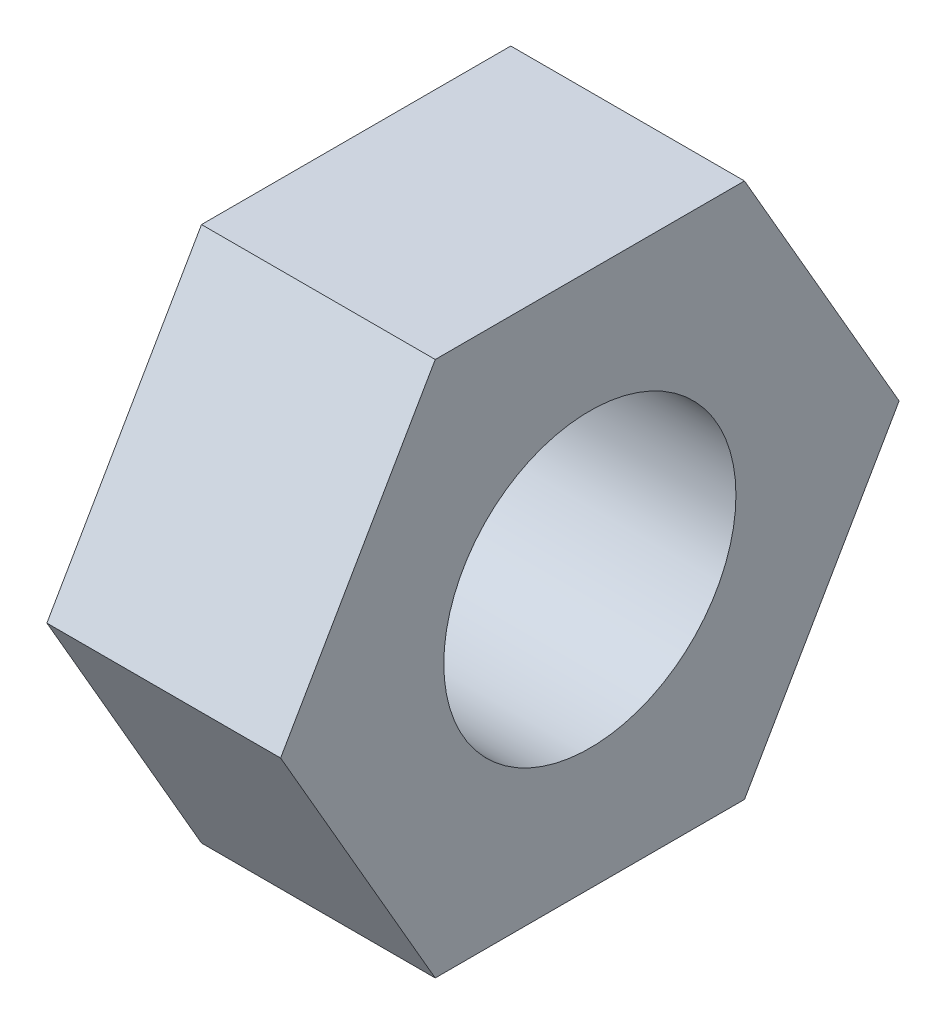
SolidWorks part; units mm, degrees
ref_plane "Front Plane" through (0, 0, 0) normal (0, 0, 1) x (1, 0, 0)
ref_plane "Top Plane" through (0, 0, 0) normal (0, 1, 0) x (1, 0, 0)
ref_plane "Right Plane" through (0, 0, 0) normal (1, 0, 0) x (0, 0, -1)
sketch "Nut Sketch" plane through (0, 0, 0) normal (1, 0, 0) x (0, 0, -1)
  line L0 (3.1754, 0) -> (1.5877, 2.75)
  line L1 (1.5877, 2.75) -> (-1.5877, 2.75)
  line L2 (-1.5877, 2.75) -> (-3.1754, 0)
  line L3 (-3.1754, 0) -> (-1.5877, -2.75)
  line L4 (-1.5877, -2.75) -> (1.5877, -2.75)
  line L5 (1.5877, -2.75) -> (3.1754, 0)
extrude "Nut" add sketch "Nut Sketch" along normal blind 2.4
ref_axis "Engine Axis" through (2.52, 0, 0) along (-1, 0, 0)
sketch "Thread Sketch" plane through (0, 0, 0) normal (0, 0, 1) x (1, 0, 0)
  line L0 (-1000, 0) -> (1000, 0) construction
  line L1 (-1, 0) -> (3.4, 0)
  line L2 (3.4, 0) -> (3.4, 1.5)
  line L3 (3.4, 1.5) -> (-1, 1.5)
  line L4 (-1, 1.5) -> (-1, 0)
revolve "Thread" cut sketch "Thread Sketch" angle 360 about L0
